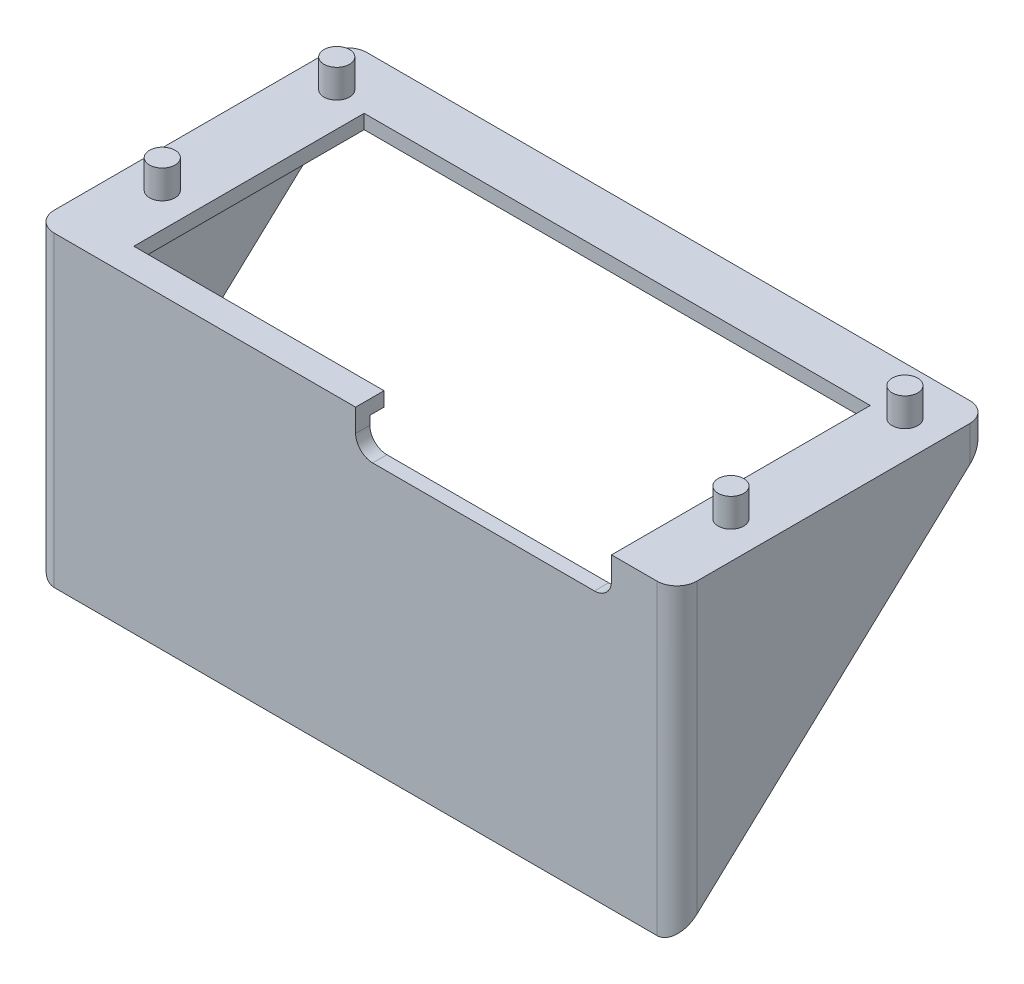
SolidWorks part; units mm, degrees
ref_plane "Front Plane" through (0, 0, 0) normal (0, 0, 1) x (1, 0, 0)
ref_plane "Top Plane" through (0, 0, 0) normal (0, 1, 0) x (1, 0, 0)
ref_plane "Right Plane" through (0, 0, 0) normal (1, 0, 0) x (0, 0, -1)
sketch "Sketch1" plane through (0, 0, 0) normal (0, 1, 0) x (1, 0, 0)
  line L1 (-52.5387, 40.0295) -> (60.4613, 40.0295)
  line L2 (-52.5387, 40.0295) -> (-52.5387, -14.9705)
  line L3 (-52.5387, -14.9705) -> (60.4613, -14.9705)
  line L4 (60.4613, 40.0295) -> (60.4613, -14.9705)
  dimension "D1" = 113
  dimension "D2" = 55
extrude "Boss-Extrude1" add sketch "Sketch1" along normal blind 3
sketch "Sketch3" plane through (60.4613, 0, 0) normal (1, 0, 0) x (0, 0, -1)
  line L0 (-14.9705, 0) -> (-14.9705, -50.9902)
  line L1 (-14.9705, -50.9902) -> (40.0295, 0)
  line L2 (40.0295, 0) -> (-14.9705, 0)
  dimension "D1" = 75
  dimension "D2" = 90
extrude "Boss-Extrude3" add sketch "Sketch3" against normal up to surface (113 mm away) up to face at (-52.5387, 1.5, -12.5295)
sketch "Sketch2" plane through (0, 3, 0) normal (0, 1, 0) x (1, 0, 0)
  line L0 (60.4613, -14.9705) -> (60.4613, 40.0295) construction
  line L1 (-52.5387, -14.9705) -> (60.4613, -14.9705) construction
  circle A0 centre (-46.0387, 31.7095) radius 2.25
  circle A1 centre (53.9613, 31.6295) radius 2.25
  circle A2 centre (53.9613, 1.0295) radius 2.25
  circle A3 centre (-46.0387, 1.0295) radius 2.25
  dimension "D1" = 4.5
  dimension "D2" = 4.5
  dimension "D3" = 4.5
  dimension "D4" = 4.5
  dimension "D5" = 100
  dimension "D6" = 100
  dimension "D7" = 6.5
  dimension "D8" = 6.5
  dimension "D9" = 30.68
  dimension "D10" = 30.6
  dimension "D11" = 16
  dimension "D12" = 16
extrude "Boss-Extrude2" add sketch "Sketch2" along normal blind 5
shell "Shell1" thickness 2.5 removed face at (3.9613, -25.4951, -12.5295)
sketch "Sketch4" plane through (0, 0.5, 0) normal (0, -1, 0) x (1, 0, 0)
  line L0 (-50.0387, -37.5295) -> (-50.0387, 12.4705) construction
  line L1 (-40.0387, 9.9705) -> (47.9613, 9.9705)
  line L2 (-40.0387, 9.9705) -> (-40.0387, -30.5295)
  line L3 (-40.0387, -30.5295) -> (47.9613, -30.5295)
  line L4 (47.9613, 9.9705) -> (47.9613, -30.5295)
  line L5 (57.9613, 12.4705) -> (57.9613, -37.5295) construction
  line L6 (57.9613, -37.5295) -> (-50.0387, -37.5295) construction
  line L7 (-50.0387, 12.4705) -> (57.9613, 12.4705) construction
  dimension "D1" = 10
  dimension "D2" = 10
  dimension "D3" = 7
  dimension "D4" = 2.5
extrude "Cut-Extrude1" cut sketch "Sketch4" against normal blind 10
fillet "Fillet2" radius 3.5 4 edges at (-52.5387, 1.5, -40.0295) (60.4613, 1.5, -40.0295) (60.4613, -23.9951, 14.9705) (-52.5387, -23.9951, 14.9705)
sketch "Sketch5" plane through (0, 0, 14.9705) normal (0, 0, 1) x (1, 0, 0)
  line L0 (-49.0387, 3) -> (56.9613, 3) construction
  line L1 (3.9613, 3) -> (48.9613, 3)
  line L2 (3.9613, 3) -> (3.9613, -4)
  line L3 (3.9613, -4) -> (48.9613, -4)
  line L4 (48.9613, 3) -> (48.9613, -4)
  line L5 (60.4613, 3) -> (60.4613, -47.7454) construction
  dimension "D1" = 11.5
  dimension "D2" = 45
  dimension "D3" = 7
extrude "Cut-Extrude2" cut sketch "Sketch5" against normal up to surface (45.5 mm away) up to face at (3.9613, 1.75, -30.5295)
fillet "Fillet3" radius 3 2 edges at (48.9613, -4, 13.7205) (3.9613, -4, 13.7205)
sketch "Sketch6" plane through (0, -19.9575, -18.5025) normal (0, -0.7333, -0.6799) x (1, 0, 0)
  line L0 (-49.0387, 45.645) -> (56.9613, 45.645) construction
  line L1 (-50.0387, 42.2359) -> (57.9613, 42.2359)
  line L2 (-50.0387, 42.2359) -> (-50.0387, -25.9459)
  line L3 (-50.0387, -25.9459) -> (57.9613, -25.9459)
  line L4 (57.9613, 42.2359) -> (57.9613, -25.9459)
  line L5 (56.9613, -29.355) -> (-49.0387, -29.355) construction
  line L6 (-52.5387, -24.5823) -> (-52.5387, 40.8723) construction
  line L7 (60.4613, 40.8723) -> (60.4613, -24.5823) construction
